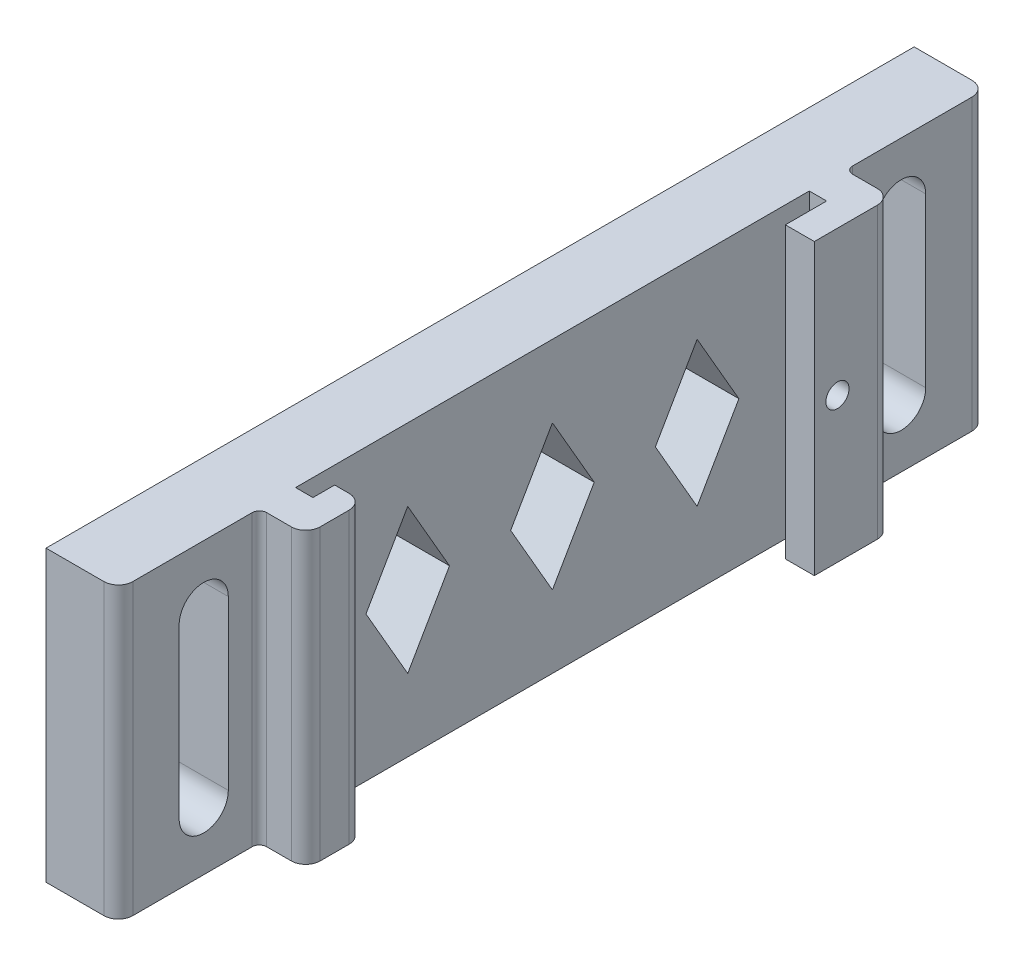
SolidWorks part; units mm, degrees
ref_plane "Front Plane" through (0, 0, 0) normal (0, 0, 1) x (1, 0, 0)
ref_plane "Top Plane" through (0, 0, 0) normal (0, 1, 0) x (1, 0, 0)
ref_plane "Right Plane" through (0, 0, 0) normal (1, 0, 0) x (0, 0, -1)
sketch "Sketch2" plane through (0, 0, 0) normal (0, 1, 0) x (1, 0, 0)
  line L0 (0, -30) -> (0, 30)
  line L1 (0, 30) -> (8.2, 30)
  line L2 (8.2, 30) -> (8.2, 16.25)
  line L3 (8.2, 16.25) -> (6.2, 16.25)
  line L4 (6.2, 16.25) -> (6.2, 17.75)
  line L5 (6.2, 17.75) -> (5, 17.75)
  line L6 (5, 17.75) -> (5, -17.75)
  line L7 (0, 0) -> (5, 0) construction
  line L8 (0, -30) -> (8.2, -30)
  line L9 (8.2, -30) -> (8.2, -16.25)
  line L10 (8.2, -16.25) -> (6.2, -16.25)
  line L11 (6.2, -16.25) -> (6.2, -17.75)
  line L12 (6.2, -17.75) -> (5, -17.75)
  dimension "D1" = 35.5
  dimension "D2" = 1.5
  dimension "D3" = 1.2
  dimension "D4" = 2
  dimension "D5" = 5
  dimension "D6" = 60
extrude "Boss-Extrude1" add sketch "Sketch2" along normal blind 20
hole_wizard "M3 Clearance Slot1" positions "Sketch3" profile "Sketch4" size "M3" standard "ANSI Metric" slot yes end condition through all
sketch "Sketch3" plane through (0, 0, 0) normal (-1, 0, 0) x (0, 0, 1)
  line L0 (-24.1, 2.5) -> (-24.1, 17.5) construction
  line L1 (-24.1, 10) -> (24.1, 10) construction
  line L5 (0, 0) -> (0, 10) construction
  line L8 (24.1, 10) -> (30, 10) construction
  line L9 (30, 20) -> (30, 0) construction
  point P0 (-24.1, 10)
  point P4 (24.1, 10)
  dimension "D1" = 15
  dimension "D2" = 48.2
sketch "Sketch4" plane through (0, 10, -24.1) normal (0, 1, 0) x (0, 0, 1)
  line L0 (0, 0) -> (0, 8.2)
  line L1 (0, 8.2) -> (1.7, 8.2)
  line L2 (1.7, 8.2) -> (1.7, 0)
  line L5 (1.7, 0) -> (0, 0)
  line L11 (0, -6.35) -> (0, 107.95) construction
  dimension "Thru Hole Dia." = 3.4
  dimension "Thru Hole Depth" = 8.2
sketch "Sketch5" plane through (0, 0, 0) normal (0, -1, 0) x (1, 0, 0)
  line L0 (8.2, 30) -> (8.2, 16.25) construction
  line L1 (8.2, 20.25) -> (5, 20.25)
  line L2 (8.2, 20.25) -> (8.2, 30)
  line L3 (8.2, 30) -> (5, 30)
  line L4 (5, 20.25) -> (5, 30)
  line L5 (0, 30) -> (8.2, 30) construction
  line L6 (5, 17.75) -> (5, -17.75) construction
  line L7 (0, 0) -> (11.6606, 0) construction
  line L8 (8.2, -20.25) -> (8.2, -30)
  line L9 (8.2, -30) -> (5, -30)
  line L10 (5, -20.25) -> (5, -30)
  line L11 (8.2, -20.25) -> (5, -20.25)
  dimension "D1" = 9.75
extrude "Cut-Extrude1" cut sketch "Sketch5" against normal through all
sketch "Sketch8" plane through (5, 0, 0) normal (1, 0, 0) x (0, 0, -1)
  line L0 (0, 5) -> (2.8868, 10)
  line L1 (2.8868, 10) -> (0, 15)
  line L2 (0, 15) -> (-2.8868, 10)
  line L3 (-2.8868, 10) -> (0, 5)
  line L4 (0, 5) -> (0, 15) construction
  line L5 (2.8868, 10) -> (-2.8868, 10) construction
  line L6 (-17.75, 0) -> (17.75, 0) construction
  line L8 (16.25, 20) -> (16.25, 0) construction
  point P4 (0, 0)
  point P13 (16.25, 10)
  dimension "D1" = 120
  dimension "D2" = 5
extrude "Cut-Extrude2" cut sketch "Sketch8" against normal through all
pattern_linear "LPattern1" count 2 spacing 10 along (0, 0, 1) of "Cut-Extrude2"
pattern_linear "LPattern2" count 2 spacing 10 along (0, 0, -1) of "Cut-Extrude2"
fillet "Fillet2" radius 0.5 2 edges at (5, 10, 20.25) (5, 10, -20.25)
sketch "Sketch9" plane through (0, 0, -16.25) normal (0, 0, 1) x (1, 0, 0)
  line L1 (8.2, 0) -> (6.2, 0)
  line L2 (8.2, 0) -> (8.2, 20)
  line L3 (8.2, 20) -> (6.2, 20)
  line L4 (6.2, 0) -> (6.2, 20)
extrude "Boss-Extrude2" add sketch "Sketch9" along normal blind 1.35
fillet "Fillet1" radius 1 5 edges at (8.2, 10, 16.25) (8.2, 10, -20.25) (8.2, 10, 20.25) (5, 10, 30) (5, 10, -30)
hole_wizard "M2x0.4 Tapped Hole1" positions "Sketch12" profile "Sketch11" tap size "M2x0.4" standard "ANSI Metric" end condition up to next
sketch "Sketch12" plane through (8.2, 0, 0) normal (1, 0, 0) x (0, 0, -1)
  line L0 (14.9, 0) -> (14.9, 20) construction
  line L1 (17.75, 20) -> (17.75, 0) construction
  point P0 (16.5, 10)
  point P5 (14.9, 10)
  dimension "D1" = 1.25
sketch "Sketch11" plane through (8.2, 10, -16.5) normal (0, 1, 0) x (0, 0, -1)
  line L0 (0, 0) -> (0, 2)
  line L1 (0, 2) -> (0.8, 2)
  line L2 (0.8, 2) -> (0.8, 0)
  line L5 (0.8, 0) -> (0, 0)
  line L11 (0, -6.35) -> (0, 107.95) construction
  dimension "Thru Tap Drill Dia." = 1.6
  dimension "Thru Tap Drill Depth" = 2
cosmetic thread "Hole Thread1" parameters "D2"=2
